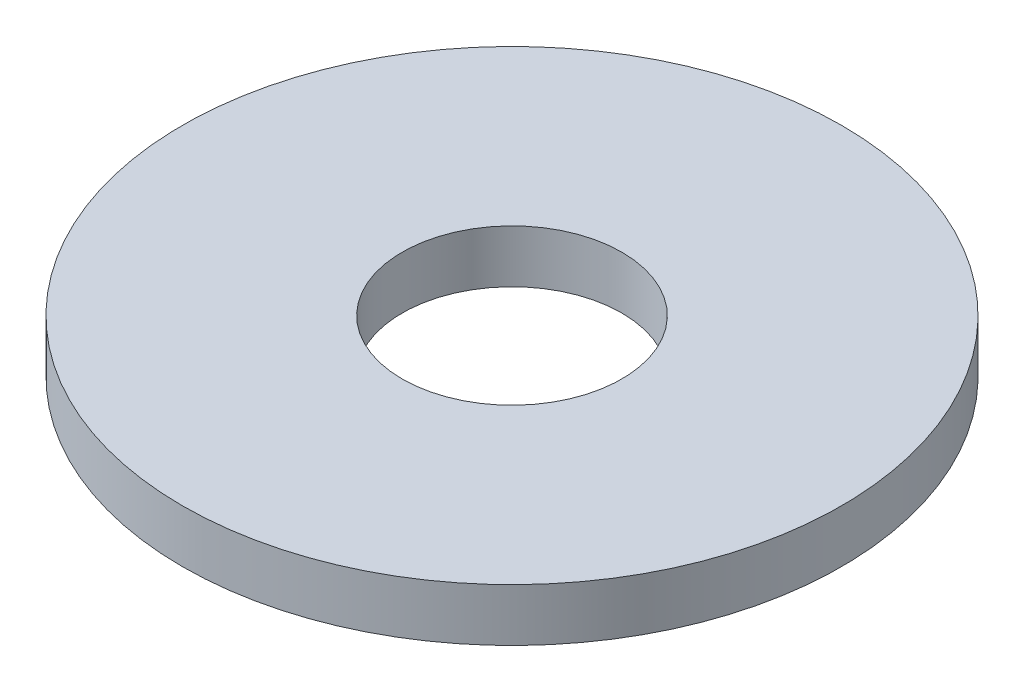
SolidWorks part; units mm, degrees
ref_plane "Front Plane" through (0, 0, 0) normal (0, 0, 1) x (1, 0, 0)
ref_plane "Top Plane" through (0, 0, 0) normal (0, 1, 0) x (1, 0, 0)
ref_plane "Right Plane" through (0, 0, 0) normal (1, 0, 0) x (0, 0, -1)
sketch "Sketch1" plane through (0, 0, 0) normal (0, 1, 0) x (1, 0, 0)
  circle A0 centre (0, 0) radius 75
  dimension "FLANGE_OD" = 150
extrude "Boss-Extrude1" add sketch "Sketch1" along normal blind 12
sketch "Sketch2" plane through (0, 0, 0) normal (0, 1, 0) x (1, 0, 0)
  circle A0 centre (0, 0) radius 25
  dimension "BORE_D" = 50
extrude "Cut-Extrude1" cut sketch "Sketch2" along normal through all
sketch "Sketch3" plane through (0, 12, 0) normal (0, 1, 0) x (1, 0, 0)
  circle A0 centre (0, 0) radius 18.2468 construction
  circle A1 centre (-18.2468, 0) radius 3.5843
  dimension "BOLT_D" = 7.1686
  dimension "BOLT_PCD" = 36.4937
extrude "Cut-Extrude2" cut sketch "Sketch3" against normal blind 11.5211 rebuild error yes
pattern_circular "CirPattern1" count 5 over 360 rebuild error yes
